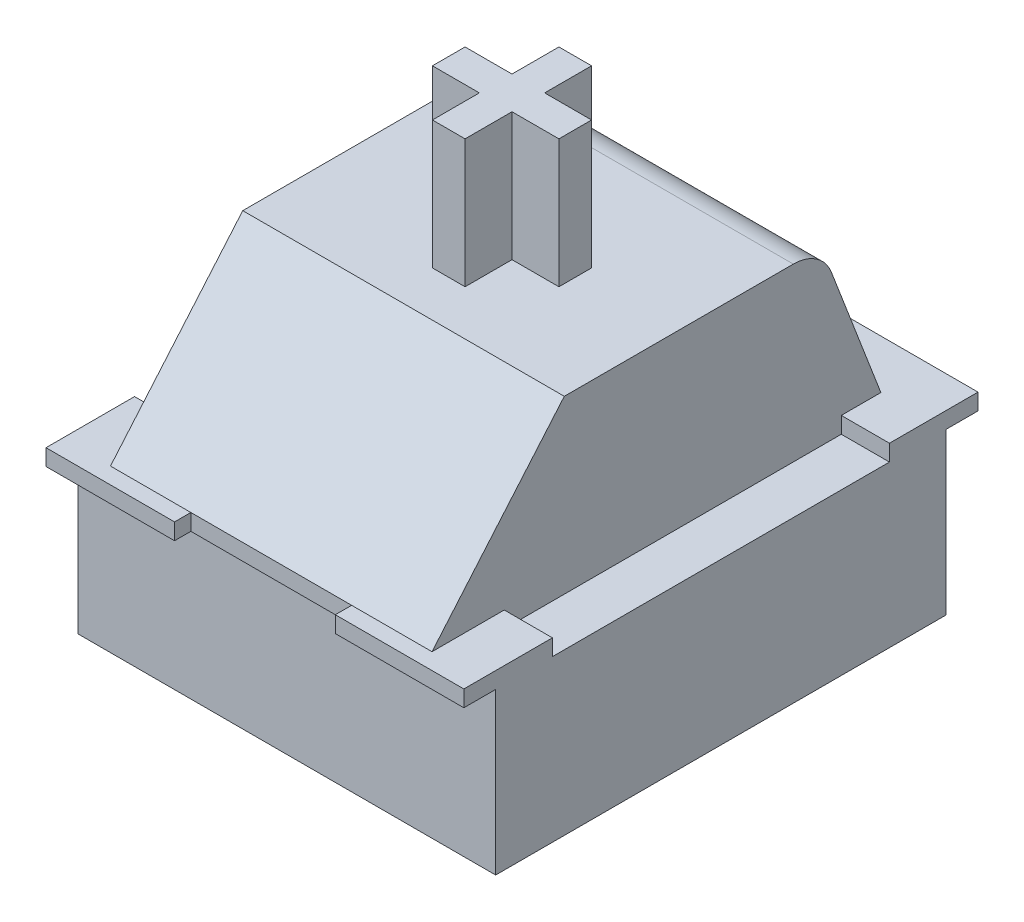
SolidWorks part; units mm, degrees
ref_plane "Alzado" through (0, 0, 0) normal (0, 0, 1) x (1, 0, 0)
ref_plane "Planta" through (0, 0, 0) normal (0, 1, 0) x (1, 0, 0)
ref_plane "Vista lateral" through (0, 0, 0) normal (1, 0, 0) x (0, 0, -1)
sketch "Croquis1" plane through (0, 0, 0) normal (1, 0, 0) x (0, 0, -1)
  line L0 (-3.3765, 7.8359) -> (-7.493, 3.0099)
  line L1 (-7.0104, -2.5019) -> (7.0104, -2.5019)
  line L2 (-7.0104, -2.5019) -> (-7.0104, 2.5019)
  line L4 (7.0104, -2.5019) -> (7.0104, 2.5019)
  line L5 (-7.493, 3.0099) -> (6.477, 3.0099)
  line L7 (-8.001, 2.5019) -> (-7.0104, 2.5019)
  line L8 (-8.001, 2.5019) -> (-8.001, 3.0099)
  line L9 (-8.001, 3.0099) -> (8.001, 3.0099)
  line L10 (8.001, 2.5019) -> (8.001, 3.0099)
  line L11 (6.477, 3.0099) -> (-3.5052, 3.0099)
  line L13 (3.7516, 7.8359) -> (-3.3765, 7.8359)
  line L15 (4.9373, 7.021) -> (6.477, 3.0099)
  line L16 (7.0104, 2.5019) -> (8.001, 2.5019)
  line L17 (-2.8685, 7.8359) -> (3.1259, 7.8359)
  line L18 (-2.8685, 7.8359) -> (-2.8685, 11.8237)
  line L19 (-2.8685, 11.8237) -> (3.1259, 11.8237)
  line L20 (3.1259, 7.8359) -> (3.1259, 11.8237)
  arc A0 (4.9373, 7.021) -> (3.7516, 7.8359) centre (3.7516, 6.5659) ccw
  point P0 (0, 0)
  point P14 (8.001, 2.7559)
  point P19 (4.6245, 7.8359)
  point P20 (-7.0104, 0)
  point P21 (0, -2.5019)
  dimension "D7" = 1.27
  dimension "D1" = 16.002
  dimension "D2" = 0.508
  dimension "D3" = 4.826
  dimension "D4" = 13.97
  dimension "D5" = 8.001
  dimension "D6" = 3.9878
  dimension "D8" = 0.9906
  dimension "D9" = 0.9906
  dimension "D10" = 5.0038
  dimension "D11" = 0.508
  dimension "D12" = 69
  dimension "D13" = 5.9944
  dimension "D14" = 3.9878
  dimension "D15" = 0.508
  dimension "D16" = 14.0208
extrude "Saliente-Extruir1" add sketch "Croquis1" along normal blind 6.5024 and the other way blind 6.5024 contours L4 L16 L10 L9 L5 L8 L7 L2 L1 region at (0, 0.2862, 0)
extrude "Saliente-Extruir2" add sketch "Croquis1<3>" along normal blind 5.0038 and the other way blind 5.0038 contours L15 A0 L13 L0 L5 L9 region at (0, 5.198, 0.005)
sketch "Croquis1<3>" plane through (0, 0, 0) normal (1, 0, 0) x (0, 0, -1) same geometry as "Croquis1"
extrude "Saliente-Extruir3" add sketch "Croquis1<4>" along normal blind 3.4671 and the other way blind 3.4671 contours L13 L20 L19 L18 region at (0, 9.8298, -0.1287)
sketch "Croquis1<4>" plane through (0, 0, 0) normal (1, 0, 0) x (0, 0, -1) same geometry as "Croquis1"
sketch "Croquis2" plane through (0, 3.0099, 0) normal (0, 1, 0) x (1, 0, 0)
  line L0 (0, -8.2448) -> (0, 8.2448) construction
  line L1 (-6.5024, -8.001) -> (6.5024, -8.001) construction
  line L2 (-2.5019, -8.001) -> (2.5019, -8.001)
  line L3 (-2.5019, -8.001) -> (-2.5019, -7.493)
  line L4 (-2.5019, -7.493) -> (2.5019, -7.493)
  line L5 (2.5019, -8.001) -> (2.5019, -7.493)
  line L6 (-5.0038, -7.493) -> (5.0038, -7.493) construction
  line L7 (-6.5024, 8.001) -> (6.5024, 8.001) construction
  line L8 (-2.5019, 8.001) -> (2.5019, 8.001)
  line L9 (-2.5019, 8.001) -> (-2.5019, 6.477)
  line L10 (-2.5019, 6.477) -> (2.5019, 6.477)
  line L11 (2.5019, 8.001) -> (2.5019, 6.477)
  line L12 (-5.0038, 6.477) -> (5.0038, 6.477) construction
  line L13 (-6.5024, -8.001) -> (-6.5024, 8.001) construction
  line L14 (-6.5024, 5.2451) -> (-5.0038, 5.2451)
  line L15 (-6.5024, 5.2451) -> (-6.5024, -5.2451)
  line L16 (-6.5024, -5.2451) -> (-5.0038, -5.2451)
  line L17 (-5.0038, 5.2451) -> (-5.0038, -5.2451)
  line L18 (-5.0038, -7.493) -> (-5.0038, 6.477) construction
  line L19 (5.0038, -7.493) -> (5.0038, 6.477) construction
  line L20 (5.0038, 5.2451) -> (6.5024, 5.2451)
  line L21 (5.0038, 5.2451) -> (5.0038, -5.2451)
  line L22 (5.0038, -5.2451) -> (6.5024, -5.2451)
  line L23 (6.5024, 5.2451) -> (6.5024, -5.2451)
  line L24 (6.5024, -8.001) -> (6.5024, 8.001) construction
  point P4 (0, 0)
  point P21 (0, 8.001)
  point P22 (0, -8.001)
  point P39 (-6.5024, 0)
  point P40 (6.5024, 0)
  dimension "D1" = 5.0038
  dimension "D2" = 5.0038
  dimension "D3" = 10.4902
  dimension "D4" = 10.4902
extrude "Cortar-Extruir1" cut sketch "Croquis2" against normal up to surface (0.508 mm away) up to face at (0, 2.5019, -7.5057)
sketch "Croquis3" plane through (0, 11.8237, 0) normal (0, 1, 0) x (1, 0, 0)
  line L0 (-3.4671, 3.1259) -> (-3.4671, -2.8685)
  line L1 (-3.4671, -2.8685) -> (-1.9685, -2.8685)
  line L2 (-3.4671, -2.8685) -> (3.4671, -2.8685) construction
  line L3 (-3.4671, 3.1259) -> (-1.9685, 3.1259)
  line L4 (-3.4671, 3.1259) -> (3.4671, 3.1259) construction
  line L5 (-3.2131, -2.6145) -> (-1.9685, -2.6145)
  line L6 (-3.2131, 2.8719) -> (-3.2131, -2.6145)
  line L7 (-3.2131, 2.8719) -> (-1.9685, 2.8719)
  line L8 (-1.9685, -2.8685) -> (-1.9685, -2.6145)
  line L9 (-1.9685, 3.1259) -> (-1.9685, 2.8719)
  line L10 (0, 0) -> (0, 5.5715) construction
  line L11 (0.508, 1.9685) -> (-0.508, 1.9685)
  line L12 (-0.508, 1.9685) -> (-0.508, 0.508)
  line L13 (-0.508, 0.508) -> (-1.9685, 0.508)
  line L14 (-1.9685, 0.508) -> (-1.9685, -0.508)
  line L15 (-1.9685, -0.508) -> (-0.508, -0.508)
  line L16 (-0.508, -0.508) -> (-0.508, -1.9685)
  line L17 (-0.508, -1.9685) -> (0.508, -1.9685)
  line L18 (3.2131, 2.8719) -> (3.2131, -2.6145)
  line L19 (3.2131, 2.8719) -> (1.9685, 2.8719)
  line L20 (1.9685, 3.1259) -> (1.9685, 2.8719)
  line L21 (3.4671, 3.1259) -> (1.9685, 3.1259)
  line L22 (3.4671, 3.1259) -> (3.4671, -2.8685)
  line L23 (3.4671, -2.8685) -> (1.9685, -2.8685)
  line L24 (1.9685, -2.8685) -> (1.9685, -2.6145)
  line L25 (3.2131, -2.6145) -> (1.9685, -2.6145)
  line L26 (0.508, -0.508) -> (0.508, -1.9685)
  line L27 (1.9685, -0.508) -> (0.508, -0.508)
  line L28 (1.9685, 0.508) -> (1.9685, -0.508)
  line L29 (0.508, 0.508) -> (1.9685, 0.508)
  line L30 (0.508, 1.9685) -> (0.508, 0.508)
  point P28 (-1.9685, 0)
  point P35 (0, -1.9685)
  point P43 (0, 1.9685)
  dimension "D2" = 0.508
  dimension "D3" = 1.016
  dimension "D4" = 0.254
  dimension "D5" = 1.4986
  dimension "D1" = 0.254
  dimension "D6" = 0.254
extrude "Cortar-Extruir2" cut sketch "Croquis3" against normal up to surface (3.9878 mm away) flip side to cut up to face at (0, 7.8359, -0.1875)
extrude "Cortar-Extruir3" cut sketch "Croquis3<2>" against normal up to surface (3.9878 mm away) contours L6 L5 L8 L1 L0 L3 L9 L7 | L22 L23 L24 L25 L18 L19 L20 L21 up to face at (2.6543, 7.8359, -0.1287)
sketch "Croquis3<2>" plane through (0, 11.8237, 0) normal (0, 1, 0) x (1, 0, 0) same geometry as "Croquis3"
